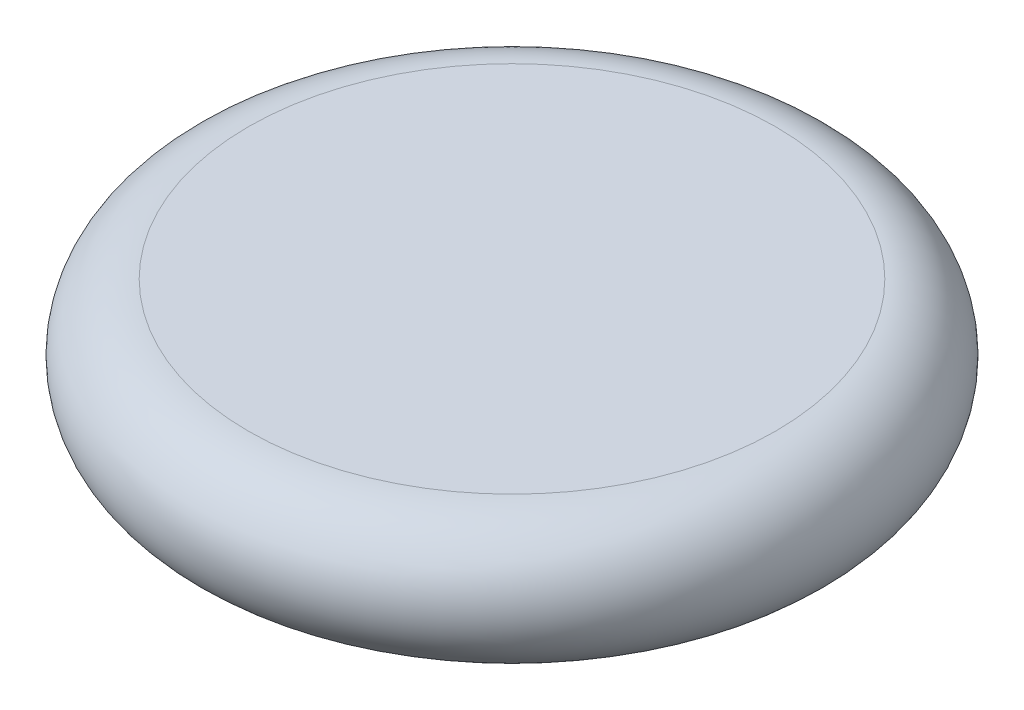
SolidWorks part; units mm, degrees
ref_plane "Front Plane" through (0, 0, 0) normal (0, 0, 1) x (1, 0, 0)
ref_plane "Top Plane" through (0, 0, 0) normal (0, 1, 0) x (1, 0, 0)
ref_plane "Right Plane" through (0, 0, 0) normal (1, 0, 0) x (0, 0, -1)
sketch "Sketch1" plane through (0, 0, 0) normal (0, 0, 1) x (1, 0, 0)
  line L0 (0, 0) -> (0, -500)
  line L1 (0, -500) -> (1000, -500)
  line L3 (0, 0) -> (1000, 0)
  arc A0 (1000, -500) -> (1000, 0) centre (1000, -250) ccw
  point P0 (0, 0)
  dimension "D1" = 1000
  dimension "D2" = 500
  dimension "D3" = 1000
ref_axis "Axis1" through (0, 550, 0) along (0, -1, 0)
revolve "Revolve2" add sketch "Sketch1" angle 360 about axis through (0, 550, 0) along (0, -1, 0)
